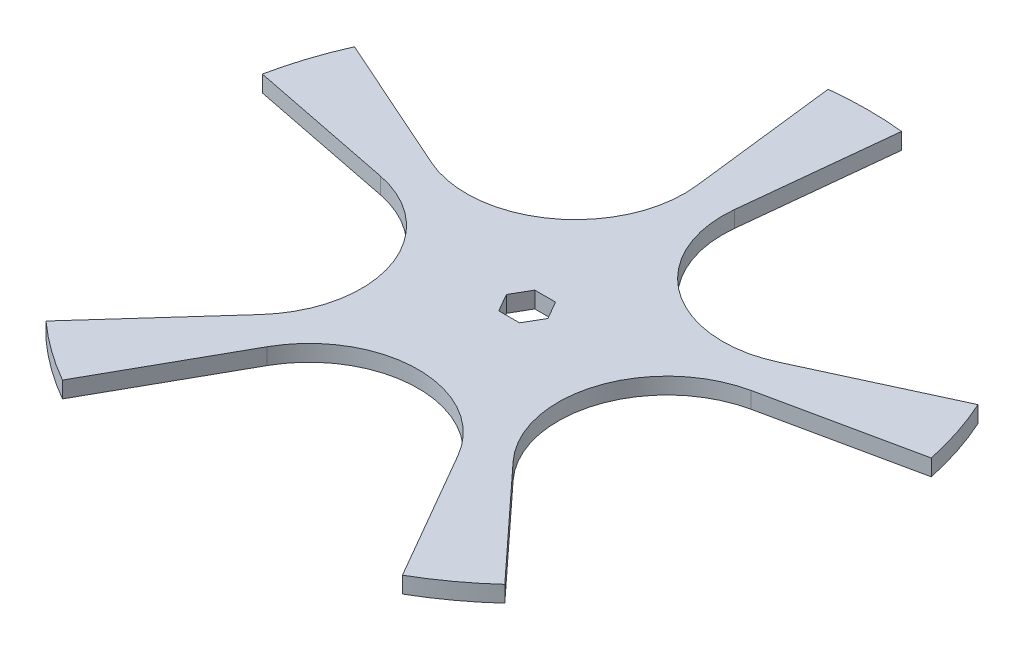
SolidWorks part; units mm, degrees
ref_plane "Front Plane" through (0, 0, 0) normal (0, 0, 1) x (1, 0, 0)
ref_plane "Top Plane" through (0, 0, 0) normal (0, 1, 0) x (1, 0, 0)
ref_plane "Right Plane" through (0, 0, 0) normal (1, 0, 0) x (0, 0, -1)
sketch "Sketch1" plane through (0, 0, 0) normal (0, 1, 0) x (1, 0, 0)
  line L0 (0, 0) -> (0, -125) construction
  line L2 (7.621, 0) -> (3.8105, 6.6)
  line L3 (3.8105, 6.6) -> (-3.8105, 6.6)
  line L4 (-3.8105, 6.6) -> (-7.621, 0)
  line L5 (-7.621, 0) -> (-3.8105, -6.6)
  line L6 (-3.8105, -6.6) -> (3.8105, -6.6)
  line L7 (3.8105, -6.6) -> (7.621, 0)
  circle A0 centre (0, 0) radius 125
  circle A6 centre (0, 0) radius 6.6 construction
  dimension "D1" = 250
  dimension "D2" = 13.2
extrude "Boss-Extrude1" add sketch "Sketch1" along normal blind 6
sketch "Sketch2" plane through (0, 6, 0) normal (0, 1, 0) x (1, 0, 0)
  line L0 (-34.9046, -60.4637) -> (-61.8585, -108.621)
  line L1 (34.641, -60) -> (62.5, -108.2532)
  line L4 (62.5, -162.1241) -> (62.5, -108.2532)
  line L6 (0, 0) -> (-61.8585, -108.621) construction
  line L7 (0, 0) -> (62.5, -108.2532) construction
  line L8 (-61.8585, -108.621) -> (-61.8585, -164.8159)
  line L9 (-61.8585, -164.8159) -> (62.5, -162.1241)
  arc A0 (34.641, -60) -> (-34.9046, -60.4637) centre (0, -80) ccw
  circle A1 centre (0, 0) radius 125 construction
  point P3 (0, 0)
extrude "Cut-Extrude1" cut sketch "Sketch2" against normal blind 6
pattern_circular "CirPattern1" count 5 over 360 about axis through (0, 6, 0) along (0, 1, 0) of "Cut-Extrude1"
